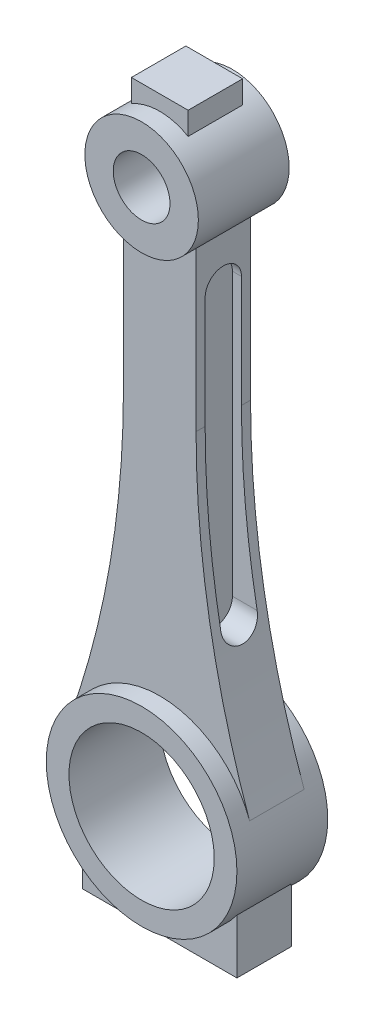
SolidWorks part; units mm, degrees
ref_plane "Front Plane" through (0, 0, 0) normal (0, 0, 1) x (1, 0, 0)
ref_plane "Top Plane" through (0, 0, 0) normal (0, 1, 0) x (1, 0, 0)
ref_plane "Right Plane" through (0, 0, 0) normal (1, 0, 0) x (0, 0, -1)
sketch "Sketch1" plane through (0, 0, 0) normal (0, 0, 1) x (1, 0, 0)
  line L0 (0, -132.9965) -> (0, -145.4965) construction
  line L1 (-8, 110.3953) -> (-8, 75.3953)
  line L2 (8, 110.3953) -> (8, 75.3953)
  line L3 (-6.25, 135.8253) -> (6.25, 135.8253)
  line L4 (6.25, 135.8253) -> (6.25, 130.8253)
  line L5 (-6.25, 135.8253) -> (-6.25, 130.8253)
  line L6 (0, 429.174) -> (0, -157.5234) construction
  line L7 (-6.25, 135.8253) -> (6.25, 135.8253)
  line L8 (-17, -24.3288) -> (17, -24.3288)
  line L9 (-17, -24.3288) -> (-17, -12.3288)
  line L10 (17, -24.3288) -> (16.9611, -12.3823)
  circle A0 centre (0, 0) radius 16
  circle A1 centre (0, 0) radius 21
  circle A2 centre (0, 120) radius 12.5
  circle A3 centre (0, 120) radius 6.25
  arc A4 (-8, 75.3953) -> (-19.7874, 7.0327) centre (-212.1328, 75.3953) cw
  arc A5 (8, 75.3953) -> (19.7874, 7.0327) centre (212.1328, 75.3953) ccw
  point P27 (0, -24.3288)
  dimension "D2" = 42
  dimension "D3" = 32
  dimension "D4" = 12.5
  dimension "D5" = 25
  dimension "D12" = 16.9611
  dimension "D1" = 120
  dimension "D6" = 8
  dimension "D7" = 35
  dimension "D8" = 12.5
  dimension "D9" = 5
  dimension "D10" = 12
  dimension "D11" = 34
extrude "Boss-Extrude1" add sketch "Sketch1" along normal mid plane 20 contours A1 A0 | A2 | A3 region at (0, 20.406, 0)
extrude "Boss-Extrude4" add sketch "Sketch1<5>" along normal mid plane 12 contours A5 L2 A2 L1 A4 A1 region at (0, 57.8448, 0)
sketch "Sketch1<5>" plane through (0, 0, 0) normal (0, 0, 1) x (1, 0, 0) same geometry as "Sketch1"
extrude "Boss-Extrude6" add sketch "Sketch1<8>" along normal mid plane 12 contours A1 L9 L8 L10 region at (-0.0336, -21.3605, 0)
sketch "Sketch1<8>" plane through (0, 0, 0) normal (0, 0, 1) x (1, 0, 0) same geometry as "Sketch1"
extrude "Boss-Extrude7" add sketch "Sketch1<9>" along normal mid plane 12 contours A2 L4 L3 L5 region at (0, 133.8599, 0)
sketch "Sketch1<9>" plane through (0, 0, 0) normal (0, 0, 1) x (1, 0, 0) same geometry as "Sketch1"
sketch "Sketch4" plane through (0, 0, 0) normal (1, 0, 0) x (0, 0, -1)
  line L0 (0, 100) -> (0, 38) construction
  line L1 (4, 100) -> (4, 38)
  line L2 (-4, 100) -> (-4, 38)
  line L4 (-10, 132.5) -> (-10, 107.5) construction
  line L5 (-10, 120) -> (13.6904, 120) construction
  arc A0 (4, 100) -> (-4, 100) centre (0, 100) ccw
  arc A1 (-4, 38) -> (4, 38) centre (0, 38) ccw
  point P3 (0, 69)
  point P12 (0, 75.3953)
  point P15 (0, 75.3953)
  point P16 (0, 75.3953)
  dimension "D2" = 20
  dimension "D1" = 62
extrude "Cut-Extrude1" cut sketch "Sketch4" along normal through all from offset 6
extrude "Cut-Extrude3" cut sketch "Sketch4<3>" against normal through all from offset 6 offset against normal yes
sketch "Sketch4<3>" plane through (0, 0, 0) normal (1, 0, 0) x (0, 0, -1) same geometry as "Sketch4"
